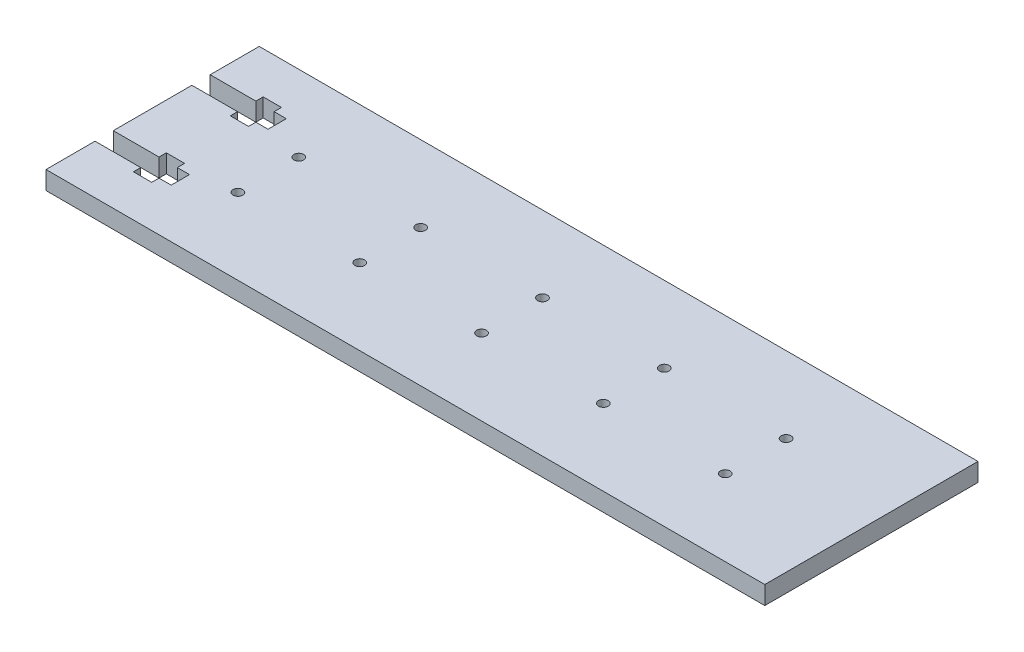
SolidWorks part; units mm, degrees
ref_plane "Front Plane" through (0, 0, 0) normal (0, 0, 1) x (1, 0, 0)
ref_plane "Top Plane" through (0, 0, 0) normal (0, 1, 0) x (1, 0, 0)
ref_plane "Right Plane" through (0, 0, 0) normal (1, 0, 0) x (0, 0, -1)
sketch "Sketch1" plane through (0, 0, 0) normal (0, 1, 0) x (1, 0, 0)
  line L1 (-118, -35) -> (118, -35)
  line L2 (-118, -35) -> (-118, 35)
  line L3 (-118, 35) -> (118, 35)
  line L4 (118, -35) -> (118, 35)
  line L5 (-118, -35) -> (118, 35) construction
  line L6 (-118, 35) -> (118, -35) construction
  circle A0 centre (80, -10) radius 1.6 construction
  circle A1 centre (80, 10) radius 1.6 construction
  circle A2 centre (40, -10) radius 1.6 construction
  circle A3 centre (40, 10) radius 1.6 construction
  circle A4 centre (0, -10) radius 1.6 construction
  circle A5 centre (0, 10) radius 1.6 construction
  circle A6 centre (-40, -10) radius 1.6 construction
  circle A7 centre (-40, 10) radius 1.6 construction
  circle A8 centre (-80, -10) radius 1.6 construction
  circle A9 centre (-80, 10) radius 1.6 construction
  circle A10 centre (80, -10) radius 1.6
  circle A11 centre (80, 10) radius 1.6
  circle A12 centre (40, -10) radius 1.6
  circle A13 centre (40, 10) radius 1.6
  circle A14 centre (0, -10) radius 1.6
  circle A15 centre (0, 10) radius 1.6
  circle A16 centre (-40, -10) radius 1.6
  circle A17 centre (-40, 10) radius 1.6
  circle A18 centre (-80, -10) radius 1.6
  circle A19 centre (-80, 10) radius 1.6
  point P0 (0, 0)
  dimension "D1" = 236
  dimension "D2" = 70
extrude "Boss-Extrude1" add sketch "Sketch1" along normal blind 6
sketch "Sketch3" plane through (0, 6, 0) normal (0, 1, 0) x (1, 0, 0)
  line L0 (-118, 0) -> (-93, 0) construction
  line L1 (-118, 35) -> (-118, -35) construction
  line L2 (-118, 15.9) -> (-93, 15.9) construction
  line L7 (-118, 12.9) -> (-103, 12.9)
  line L8 (-118, 18.9) -> (-103, 18.9)
  line L9 (-118, 12.9) -> (-118, 18.9)
  line L10 (-93, 12.9) -> (-93, 18.9)
  line L18 (-103, 10.5) -> (-97, 10.5)
  line L19 (-103, 10.5) -> (-103, 12.9)
  line L20 (-103, 21.3) -> (-97, 21.3)
  line L21 (-97, 10.5) -> (-97, 12.9)
  line L22 (-103, 10.5) -> (-97, 21.3) construction
  line L23 (-103, 21.3) -> (-97, 10.5) construction
  line L29 (-97, 18.9) -> (-97, 21.3)
  line L30 (-97, 18.9) -> (-93, 18.9)
  line L31 (-118, 18.9) -> (-93, 18.9) construction
  line L32 (-97, 12.9) -> (-93, 12.9)
  line L33 (-118, 12.9) -> (-93, 12.9) construction
  line L34 (-103, 18.9) -> (-103, 21.3)
  line L35 (-103, -21.3) -> (-97, -10.5) construction
  line L36 (-103, -10.5) -> (-97, -21.3) construction
  line L37 (-118, -15.9) -> (-93, -15.9) construction
  line L38 (-103, -18.9) -> (-103, -21.3)
  line L39 (-97, -12.9) -> (-93, -12.9)
  line L40 (-97, -18.9) -> (-93, -18.9)
  line L41 (-97, -18.9) -> (-97, -21.3)
  line L42 (-97, -10.5) -> (-97, -12.9)
  line L43 (-103, -21.3) -> (-97, -21.3)
  line L44 (-103, -10.5) -> (-103, -12.9)
  line L45 (-103, -10.5) -> (-97, -10.5)
  line L46 (-93, -12.9) -> (-93, -18.9)
  line L47 (-118, -12.9) -> (-118, -18.9)
  line L48 (-118, -18.9) -> (-103, -18.9)
  line L49 (-118, -12.9) -> (-103, -12.9)
  point P11 (-100, 15.9)
  point P47 (-100, -15.9)
  dimension "D3" = 15
  dimension "D4" = 15.9
  dimension "D7" = 25
  dimension "D1" = 10.8
  dimension "D2" = 6
  dimension "D5" = 3
  dimension "D6" = 3
extrude "Cut-Extrude2" cut sketch "Sketch3" against normal through all
